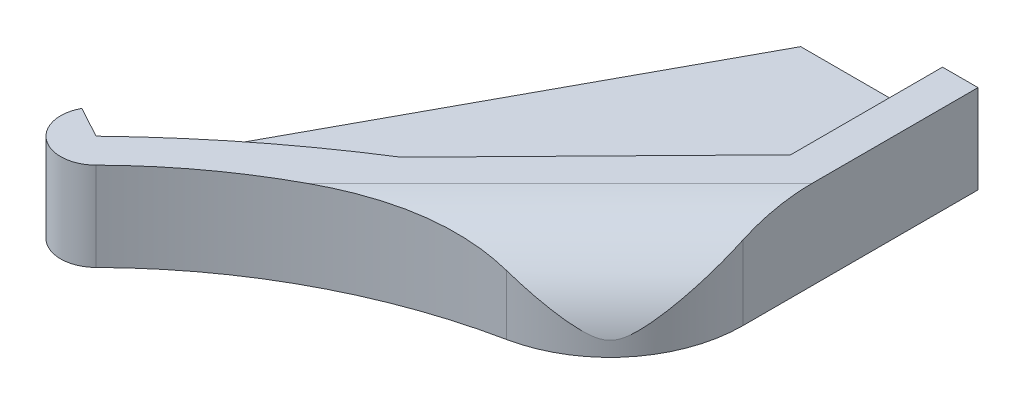
SolidWorks part; units mm, degrees
ref_plane "Front Plane" through (0, 0, 0) normal (0, 0, 1) x (1, 0, 0)
ref_plane "Top Plane" through (0, 0, 0) normal (0, 1, 0) x (1, 0, 0)
ref_plane "Right Plane" through (0, 0, 0) normal (1, 0, 0) x (0, 0, -1)
sketch "Sketch2" plane through (0, 0, 0) normal (0, 1, 0) x (1, 0, 0)
  line L0 (0, 0) -> (0, 25.4)
  line L1 (-30.8078, -7.9914) -> (-12.7, 25.4)
  line L2 (-12.7, 25.4) -> (0, 25.4)
  line L3 (0, 0) -> (6.35, 0) construction
  line L4 (0, 0) -> (-17.1655, 17.1655) construction
  arc A1 (0, 0) -> (-26.7891, -11.0084) centre (0, -38.1) ccw
  arc A2 (-26.7891, -11.0084) -> (-30.8078, -7.9914) centre (-28.575, -9.2023) cw
  dimension "D1" = 38.1
  dimension "D6" = 2.54
  dimension "D3" = 25.4
  dimension "D4" = 12.7
  dimension "D5" = 28.575
  dimension "D2" = 6.35
  dimension "D7" = 45
extrude "Boss-Extrude1" add sketch "Sketch2" along normal blind 6.35
fillet "Fillet1" radius 9.525 1 edges at (0, 3.175, 0)
ref_axis "Axis1" through (0, 6.6675, 0) along (0, -1, 0)
ref_plane "Plane1" through (0, 0, 0) normal (0.7071, 0, -0.7071) x (-0.7071, 0, -0.7071)
sketch "Sketch3" plane through (0, 0, 0) normal (0.7071, 0, -0.7071) x (-0.7071, 0, -0.7071)
  line L0 (0, 0) -> (17.9605, 0) construction
  line L1 (11.1586, 6.35) -> (4.8438, 6.35) construction
  line L2 (9.525, 6.35) -> (9.525, 7.8108)
  line L3 (9.525, 7.8108) -> (2.2067, 7.8108)
  line L4 (2.2067, 7.8108) -> (2.2067, 0)
  line L5 (2.2067, 0) -> (3.175, 0)
  arc A0 (9.525, 6.35) -> (3.175, 0) centre (9.525, 0) ccw
  dimension "D1" = 9.525
extrude "Cut-Extrude1" cut sketch "Sketch3" against normal through all both and the other way through all
sketch "Sketch4" plane through (0, 6.35, 0) normal (0, 1, 0) x (1, 0, 0)
  line L0 (-16.3371, 0.422) -> (-2.54, 14.5225)
  line L2 (-17.9795, -4.5091) -> (0, 13.4704) construction
  line L4 (-2.54, 14.5225) -> (-2.54, 25.4)
  line L5 (-28.575, -9.2023) -> (-30.8078, -7.9914)
  line L7 (0, 0) -> (0, 25.4) construction
  line L8 (0, 13.4704) -> (0, 25.4) construction
  line L9 (-17.9795, -4.5091) -> (0, 13.4704) construction
  line L10 (-12.7, 25.4) -> (-2.54, 25.4)
  line L11 (-30.8078, -7.9914) -> (-12.7, 25.4)
  line L12 (-30.8078, -7.9914) -> (-12.7, 25.4) construction
  arc A0 (-30.8078, -7.9914) -> (-26.7891, -11.0084) centre (-28.575, -9.2023) ccw construction
  arc A1 (0, 0) -> (-26.7891, -11.0084) centre (0, -38.1) ccw construction
  arc A2 (-30.8078, -7.9914) -> (-26.7891, -11.0084) centre (-28.575, -9.2023) ccw construction
  arc A3 (-17.9795, -4.5091) -> (-26.7891, -11.0084) centre (0, -38.1) ccw construction
  arc A5 (-28.575, -9.2023) -> (-16.3371, 0.422) centre (24.4021, -63.9733) cw
  dimension "D2" = 76.2
extrude "Cut-Extrude2" cut sketch "Sketch4" against normal blind 3.81
equation "\"rocket_diam\" = 3in"
equation "\"D1@Sketch2\"=\"rocket_diam\"/2"
equation "\"D2@Sketch4\"=\"rocket_diam\""
